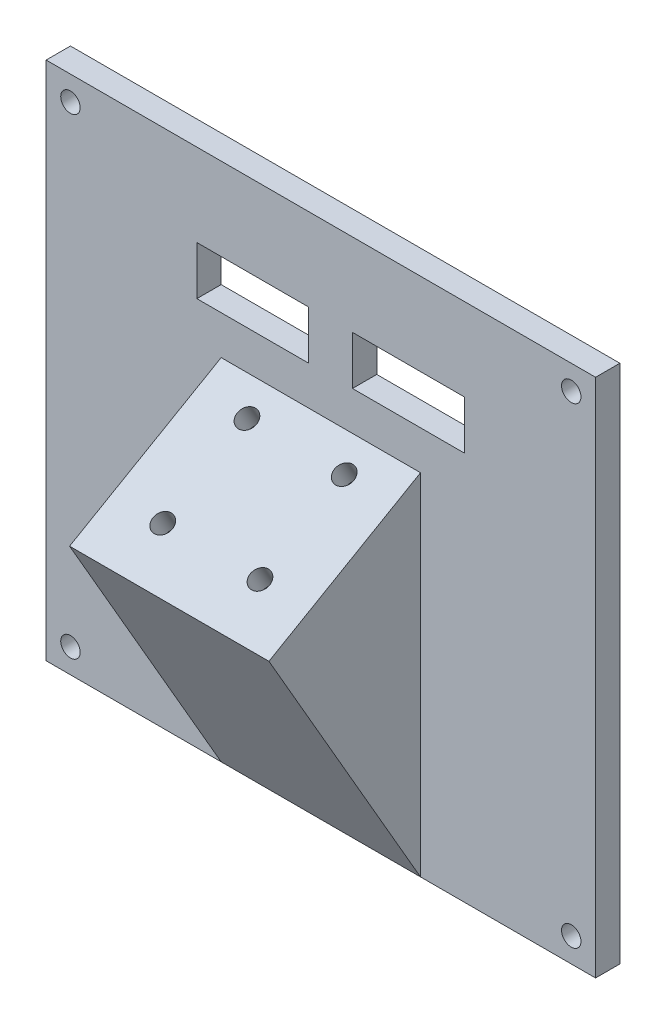
SolidWorks part; units mm, degrees
ref_plane "Front Plane" through (0, 0, 0) normal (0, 0, 1) x (1, 0, 0)
ref_plane "Top Plane" through (0, 0, 0) normal (0, 1, 0) x (1, 0, 0)
ref_plane "Right Plane" through (0, 0, 0) normal (1, 0, 0) x (0, 0, -1)
sketch "Sketch1" plane through (0, 0, 0) normal (0, 0, 1) x (1, 0, 0)
  line L1 (-56.5, -53.5) -> (56.5, -53.5)
  line L2 (-56.5, -53.5) -> (-56.5, 53.5)
  line L3 (-56.5, 53.5) -> (56.5, 53.5)
  line L4 (56.5, -53.5) -> (56.5, 53.5)
  line L5 (-56.5, -53.5) -> (56.5, 53.5) construction
  line L6 (-56.5, 53.5) -> (56.5, -53.5) construction
  point P0 (0, 0)
  dimension "D1" = 113
  dimension "D2" = 107
extrude "Boss-Extrude1" add sketch "Sketch1" along normal blind 20
sketch "Sketch2" plane through (0, 0, 0) normal (0, 0, -1) x (-1, 0, 0)
  line L5 (-46.5, 43.5) -> (46.5, 43.5)
  line L6 (-46.5, 43.5) -> (-46.5, -43.5)
  line L9 (-46.5, -43.5) -> (46.5, -43.5)
  line L10 (46.5, 43.5) -> (46.5, -43.5)
  line L11 (-46.5, 43.5) -> (46.5, -43.5) construction
  line L12 (-46.5, -43.5) -> (46.5, 43.5) construction
  point P0 (0, 0)
  dimension "D1" = 93
  dimension "D2" = 87
extrude "Cut-Extrude1" cut sketch "Sketch2" against normal blind 15
sketch "Sketch7" plane through (0, 0, 15) normal (0, 0, -1) x (-1, 0, 0)
  line L0 (46.5, 43.5) -> (-46.5, 43.5) construction
  line L5 (46.5, -43.5) -> (46.5, 43.5) construction
  line L14 (-18, 31.5) -> (14, 31.5) construction
  line L15 (-29.5, 26.5) -> (-6.5, 26.5)
  line L16 (-29.5, 26.5) -> (-29.5, 36.5)
  line L17 (-29.5, 36.5) -> (-6.5, 36.5)
  line L18 (-6.5, 26.5) -> (-6.5, 36.5)
  line L19 (-29.5, 26.5) -> (-6.5, 36.5) construction
  line L20 (-29.5, 36.5) -> (-6.5, 26.5) construction
  line L21 (2.5, 26.5) -> (25.5, 26.5)
  line L22 (2.5, 26.5) -> (2.5, 36.5)
  line L23 (2.5, 36.5) -> (25.5, 36.5)
  line L24 (25.5, 26.5) -> (25.5, 36.5)
  line L25 (2.5, 26.5) -> (25.5, 36.5) construction
  line L26 (2.5, 36.5) -> (25.5, 26.5) construction
  point P14 (-18, 31.5)
  point P19 (14, 31.5)
  dimension "D1" = 7
  dimension "D2" = 9
  dimension "D3" = 21
  dimension "D6" = 23
  dimension "D7" = 23
  dimension "D8" = 10
  dimension "D9" = 10
ref_plane "Plane2" through (0, 0, 0) normal (-1, 0, 0) x (0, 0, 1)
sketch "Sketch9" plane through (0, 0, 0) normal (-1, 0, 0) x (0, 0, 1)
  line L0 (20, -53.5) -> (51.1769, 0.5)
  line L1 (51.1769, 0.5) -> (20, 18.5)
  line L2 (20, 53.5) -> (20, -53.5) construction
  line L3 (20, 18.5) -> (20, -53.5)
  dimension "D1" = 36
  dimension "D2" = 30
extrude "Boss-Extrude4" add sketch "Sketch9" along normal mid plane 41
extrude "Cut-Extrude2" cut sketch "Sketch7" against normal blind 41
sketch "Sketch10" plane through (0, 0, 0) normal (0, 0, -1) x (-1, 0, 0)
  line L0 (-56.5, 53.5) -> (56.5, 53.5) construction
  line L1 (-56.5, -53.5) -> (-56.5, 53.5) construction
  line L2 (56.5, 53.5) -> (56.5, -53.5) construction
  line L3 (56.5, -53.5) -> (-56.5, -53.5) construction
  circle A0 centre (-51.5, 48.5) radius 2
  circle A1 centre (51.5, 48.5) radius 2
  circle A2 centre (51.5, -48.5) radius 2
  circle A3 centre (-51.5, -48.5) radius 2
  dimension "D9" = 4
  dimension "D1" = 5
  dimension "D2" = 5
  dimension "D3" = 5
  dimension "D4" = 5
  dimension "D5" = 5
  dimension "D6" = 5
  dimension "D7" = 5
  dimension "D8" = 5
extrude "Cut-Extrude3" cut sketch "Sketch10" against normal through all
sketch "Sketch11" plane through (0, 0, 10) normal (0, 0, -1) x (-1, 0, 0)
  line L0 (-51.5, -53) -> (-56.5, -53)
  line L1 (-56.5, -53.5) -> (-56.5, 53.5) construction
  line L2 (-56.5, -53) -> (-56.5, -44)
  line L3 (-56.5, -44) -> (-51.5, -44)
  line L4 (0, -53.5) -> (0, 53.5) construction
  line L5 (56.5, -53.5) -> (-56.5, -53.5) construction
  line L6 (-56.5, 53.5) -> (56.5, 53.5) construction
  line L7 (-56.5, 0) -> (56.5, 0) construction
  line L8 (56.5, 53.5) -> (56.5, -53.5) construction
  line L9 (-56.5, 44) -> (-51.5, 44)
  line L10 (-56.5, 53) -> (-56.5, 44)
  line L11 (-51.5, 53) -> (-56.5, 53)
  line L12 (51.5, 53) -> (56.5, 53)
  line L13 (56.5, 53) -> (56.5, 44)
  line L14 (56.5, 44) -> (51.5, 44)
  line L15 (56.5, -44) -> (51.5, -44)
  line L16 (56.5, -53) -> (56.5, -44)
  line L17 (51.5, -53) -> (56.5, -53)
  arc A0 (-51.5, -53) -> (-51.5, -44) centre (-51.5, -48.5) ccw
  arc A1 (-51.5, 53) -> (-51.5, 44) centre (-51.5, 48.5) cw
  arc A2 (51.5, 53) -> (51.5, 44) centre (51.5, 48.5) ccw
  arc A3 (51.5, -53) -> (51.5, -44) centre (51.5, -48.5) cw
  dimension "D1" = 4.5
extrude "Cut-Extrude4" [suppressed] cut sketch "Sketch11" along normal blind 3
sketch "Sketch12" plane through (0, 22.5353, 13.0107) normal (0, 0.866, 0.5) x (1, 0, 0)
  line L0 (-10, -14.0705) -> (10, -14.0705) construction
  line L1 (10, -14.0705) -> (10, -34.0705) construction
  line L2 (-10, -14.0705) -> (-10, -34.0705) construction
  line L3 (-10, -34.0705) -> (10, -34.0705) construction
  line L4 (0, -3.0705) -> (0, -44.0705) construction
  line L6 (-20.5, -44.0705) -> (20.5, -44.0705) construction
  circle A0 centre (-10, -14.0705) radius 2
  circle A1 centre (10, -14.0705) radius 2
  circle A2 centre (-10, -34.0705) radius 2
  circle A3 centre (10, -34.0705) radius 2
  point P14 (0, -14.0705)
  dimension "D1" = 4
  dimension "D2" = 20
  dimension "D3" = 10
  dimension "D4" = 20
extrude "Cut-Extrude5" cut sketch "Sketch12" against normal through all
sketch "Sketch15" plane through (0, 0, 15) normal (0, 0, -1) x (-1, 0, 0)
  line L1 (-59.1814, -55.5706) -> (59.1814, -55.5706)
  line L2 (-59.1814, -55.5706) -> (-59.1814, 55.5706)
  line L3 (-59.1814, 55.5706) -> (59.1814, 55.5706)
  line L4 (59.1814, -55.5706) -> (59.1814, 55.5706)
  line L5 (-59.1814, -55.5706) -> (59.1814, 55.5706) construction
  line L6 (-59.1814, 55.5706) -> (59.1814, -55.5706) construction
  point P0 (0, 0)
extrude "Cut-Extrude7" cut sketch "Sketch15" along normal through all
ref_plane "Plane3" through (0, 18.2051, 10.5107) normal (0, 0.866, 0.5) x (1, 0, 0)
sketch "Sketch17" plane through (0, 18.2051, 10.5107) normal (0, 0.866, 0.5) x (1, 0, 0)
  circle A0 centre (10, -34.0705) radius 5
  circle A1 centre (-10, -34.0705) radius 5
  circle A2 centre (-10, -14.0705) radius 5
  circle A3 centre (10, -14.0705) radius 5
  dimension "D1" = 10
extrude "Cut-Extrude8" cut sketch "Sketch17" against normal through all
sketch "Sketch19" plane through (-56.5, 0, 0) normal (-1, 0, 0) x (0, 0, 1)
  line L0 (19.994, -53.5104) -> (15, 53.5)
  line L1 (20, -53.5) -> (51.1769, 0.5) construction
  line L2 (15, 53.5) -> (67.4541, 28.6928)
  line L3 (67.4541, 28.6928) -> (19.994, -53.5104)
  point P4 (15, 53.5)
